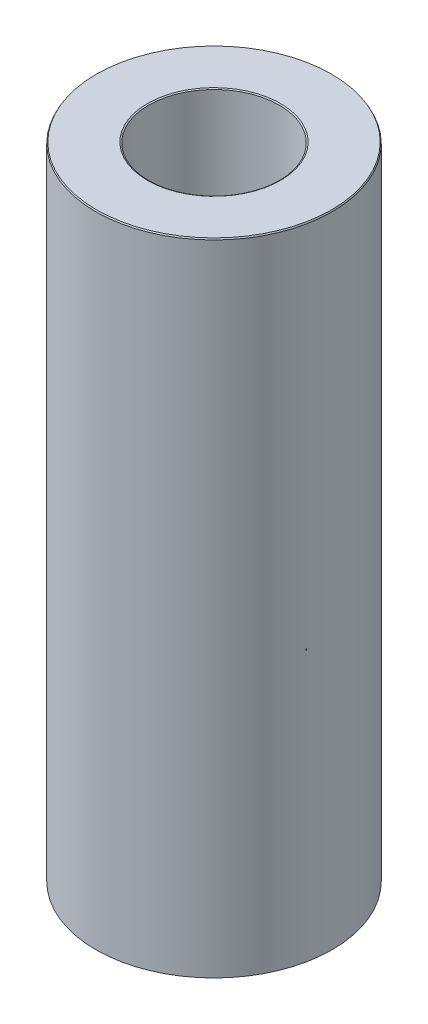
SolidWorks part; units mm, degrees
ref_plane "Front Plane" through (0, 0, 0) normal (0, 0, 1) x (1, 0, 0)
ref_plane "Top Plane" through (0, 0, 0) normal (0, 1, 0) x (1, 0, 0)
ref_plane "Right Plane" through (0, 0, 0) normal (1, 0, 0) x (0, 0, -1)
sketch "Sketch1" plane through (0, 0, 0) normal (0, 1, 0) x (1, 0, 0)
  circle A0 centre (0, 0) radius 60
  dimension "SLEEVE_OD" = 120
extrude "Boss-Extrude1" add sketch "Sketch1" along normal blind 325.2635
sketch "Sketch2" plane through (0, 0, 0) normal (0, 1, 0) x (1, 0, 0)
  circle A0 centre (0, 0) radius 33.1363
  dimension "BORE_D" = 66.2726
extrude "Cut-Extrude1" cut sketch "Sketch2" along normal through all
chamfer "Chamfer1" distance 0.6455 angle 30 4 edges at (0, 325.2635, 33.1363) (0, 0, 33.1363) (0, 0, 60) (0, 325.2635, 60) first distance on face at (0, 325.2635, 33.1363) first distance on face at (0, 0, 33.1363) first distance on face at (0, 325.2635, 60)
